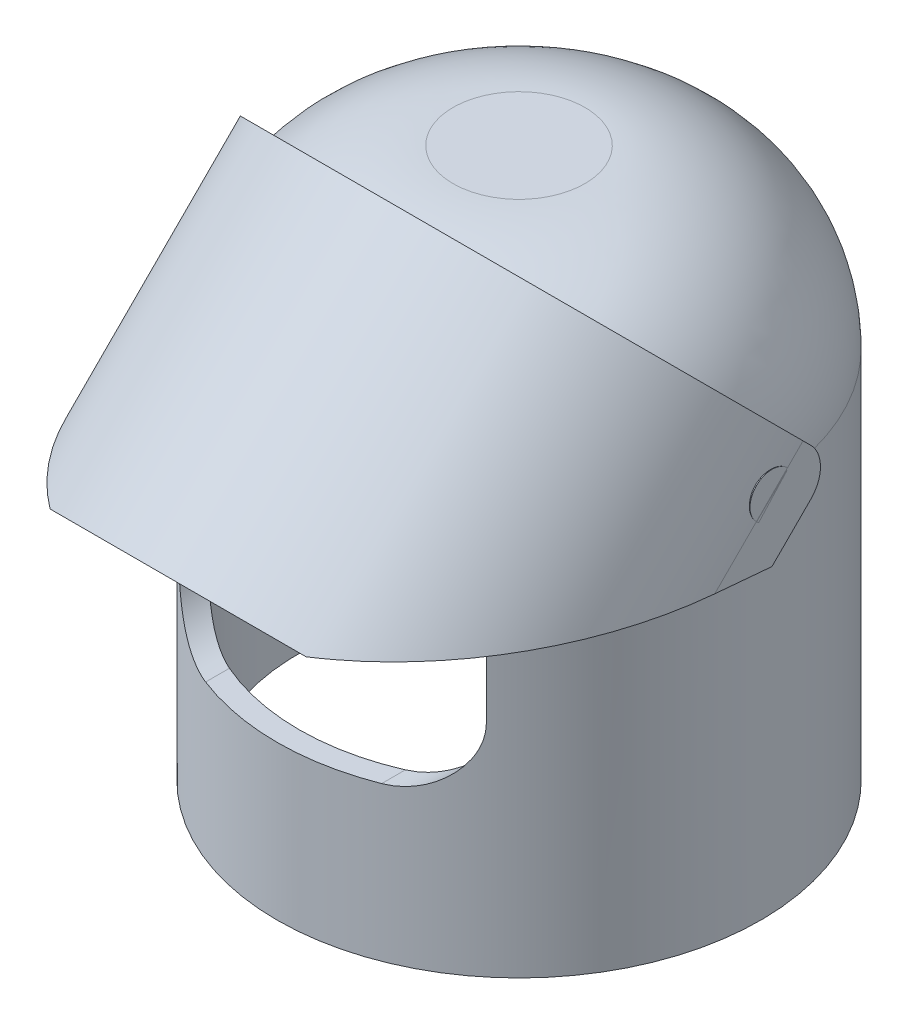
SolidWorks part; units mm, degrees
material "Natural Rubber"
ref_plane "Front Plane" through (0, 0, 0) normal (0, 0, 1) x (1, 0, 0)
ref_plane "Top Plane" through (0, 0, 0) normal (0, 1, 0) x (1, 0, 0)
ref_plane "Right Plane" through (0, 0, 0) normal (1, 0, 0) x (0, 0, -1)
sketch "Sketch2" plane through (0, 0, 0) normal (0, 1, 0) x (1, 0, 0)
  circle A1 centre (0, 0) radius 11
  dimension "D2" = 22
extrude "Boss-Extrude1" add sketch "Sketch2" along normal blind 25
fillet "Fillet1" radius 8 1 edges at (0, 25, 11)
shell "Shell1" thickness 1 removed face at (0, 0, 11)
sketch "Sketch3" plane through (0, 0, 0) normal (0, 0, 1) x (1, 0, 0)
  line L0 (0, -11) -> (0, 11) construction
  line L1 (-4, 7) -> (4, 7)
  line L2 (-7, 10) -> (-7, 14)
  line L3 (-4, 17) -> (4, 17)
  line L4 (7, 10) -> (7, 14)
  line L5 (-7, 7) -> (7, 17) construction
  line L6 (-7, 17) -> (7, 7) construction
  arc A0 (4, 7) -> (7, 10) centre (4, 10) ccw
  arc A1 (7, 14) -> (4, 17) centre (4, 14) ccw
  arc A2 (-4, 7) -> (-7, 10) centre (-4, 10) cw
  arc A3 (-4, 17) -> (-7, 14) centre (-4, 14) ccw
  point P0 (0, 12)
  point P5 (0, 0)
  dimension "D4" = 3
  dimension "D1" = 12
  dimension "D2" = 10
  dimension "D3" = 14
extrude "Cut-Extrude1" cut sketch "Sketch3" along normal blind 20
ref_plane "Plane1" through (11.5, 0, 0) normal (1, 0, 0) x (0, 0, -1)
sketch "Sketch4" plane through (11.5, 0, 0) normal (1, 0, 0) x (0, 0, -1)
  circle A0 centre (0, 17) radius 1
  dimension "D2" = 2
  dimension "D1" = 17
extrude "Boss-Extrude2" add sketch "Sketch4" against normal up to next
mirror "Mirror1" about plane through (0, 0, 0) normal (1, 0, 0) of "Boss-Extrude2"
ref_axis "Axis2" through (-11.8818, 17, 0) along (1, 0, 0)
ref_plane "Face Shield Plane" through (0, 8.5, -8.5) normal (0, -0.7071, 0.7071) x (1, 0, 0)
sketch "Sketch9" plane through (0, 8.5, -8.5) normal (0, -0.7071, 0.7071) x (1, 0, 0)
  line L0 (0, -12.1) -> (0, 12.1) construction
  line L1 (-11, 12.0208) -> (-11, 10.0208)
  line L2 (-11, 11.3137) -> (-11, 0) construction
  line L3 (11, 12.0208) -> (11, 10.0208)
  line L4 (11, 0) -> (11, 11.3137) construction
  line L5 (-11.5, 12.0208) -> (-11.5, 10.0208)
  line L6 (11.5, 12.0208) -> (11.5, 10.0208)
  line L7 (-11.5, 10.0208) -> (-11, 10.0208)
  line L8 (11, 10.0208) -> (11.5, 10.0208)
  line L9 (-11.8818, 12.0208) -> (11.5, 12.0208) construction
  arc A0 (-11, 12.0208) -> (11, 12.0208) centre (0, 12.0208) cw
  arc A1 (-11.5, 12.0208) -> (11.5, 12.0208) centre (0, 12.0208) cw
  point P0 (0, 12.0208)
  point P17 (0, 0)
  point P20 (0, 0)
  point P21 (0, 0)
  dimension "D1" = 11
  dimension "D2" = 2
  dimension "D3" = 2
  dimension "D4" = 0.5
extrude "FACE SHIELD" add sketch "Sketch9" along normal blind 12 and the other way blind 2 separate body
fillet "Fillet3" radius 1.5 2 edges at (11.25, 17, -2.8284) (-11.25, 17, -2.8284)
chamfer "Chamfer2" distance 10 angle 50 2 edges at (-11.25, 7.1005, 7.0711) (11.25, 7.1005, 7.0711) first distance on face at (-11.25, 11.5199, 2.6517) first distance on face at (11.25, 11.5199, 2.6517)
equation "\"D3@Sketch9\"=\"D2@Sketch9\""
